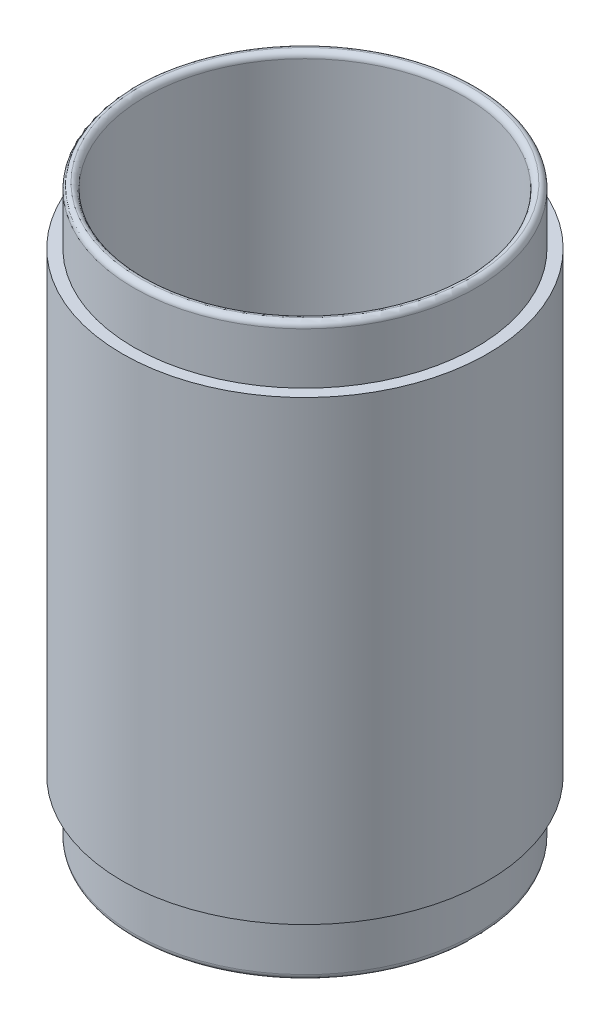
SolidWorks part; units mm, degrees
ref_plane "Front Plane" through (0, 0, 0) normal (0, 0, 1) x (1, 0, 0)
ref_plane "Top Plane" through (0, 0, 0) normal (0, 1, 0) x (1, 0, 0)
ref_plane "Right Plane" through (0, 0, 0) normal (1, 0, 0) x (0, 0, -1)
sketch "Sketch1" plane through (0, 0, 0) normal (0, 1, 0) x (1, 0, 0)
  circle A0 centre (0, 0) radius 16
  circle A1 centre (0, 0) radius 14
  dimension "D1" = 28
  dimension "D2" = 32
extrude "Boss-Extrude1" add sketch "Sketch1" along normal blind 40
sketch "Sketch2" plane through (0, 40, 0) normal (0, 1, 0) x (1, 0, 0)
  circle A0 centre (0, 0) radius 15
  circle A1 centre (0, 0) radius 14 construction
  circle A2 centre (0, 0) radius 14
  dimension "D1" = 30
extrude "Boss-Extrude2" add sketch "Sketch2" along normal blind 5
sketch "Sketch3" plane through (0, 0, 0) normal (0, -1, 0) x (1, 0, 0)
  circle A0 centre (0, 0) radius 15
  circle A1 centre (0, 0) radius 14 construction
  circle A2 centre (0, 0) radius 14
  dimension "D1" = 30
extrude "Boss-Extrude3" add sketch "Sketch3" along normal blind 5
fillet "Fillet1" radius 0.5 4 edges at (0, -5, -15) (0, 45, 15) (0, 45, 14) (0, -5, -14)
